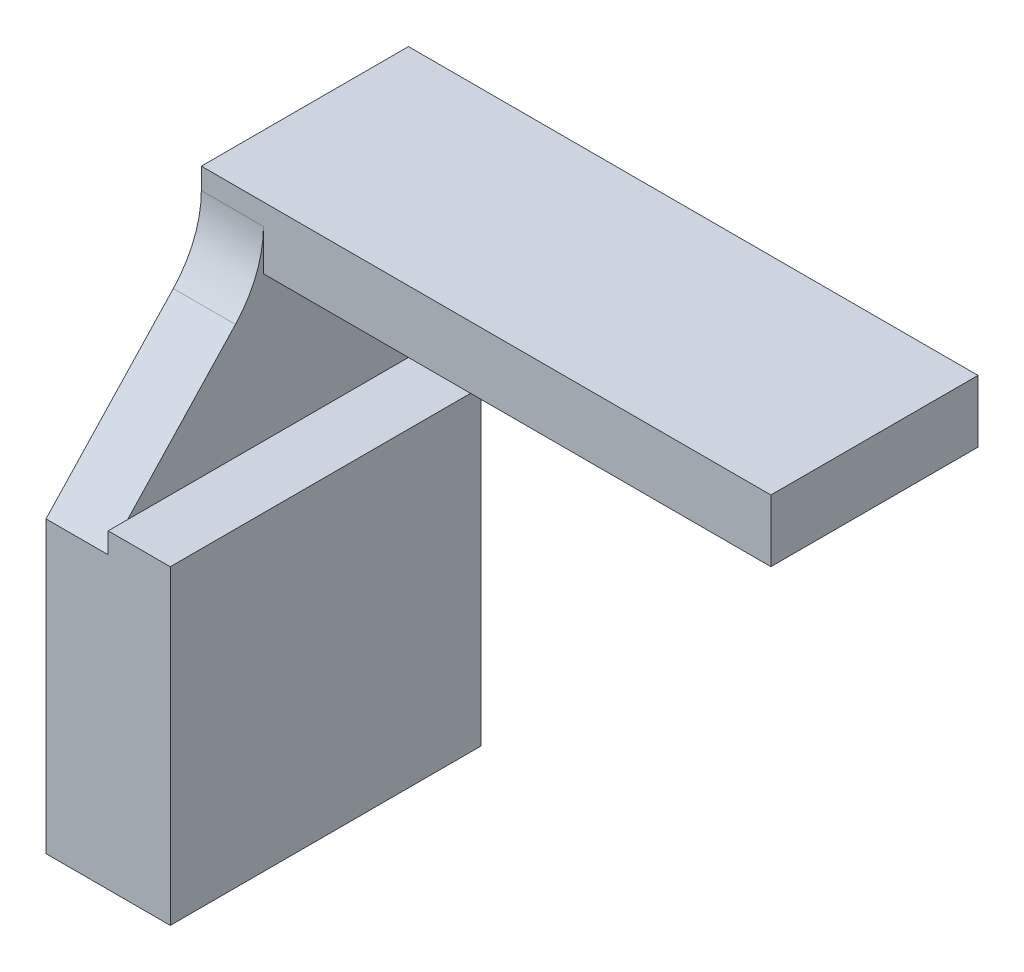
SolidWorks part; units mm, degrees
material "1060 Alloy"
ref_plane "Front Plane" through (0, 0, 0) normal (0, 0, 1) x (1, 0, 0)
ref_plane "Top Plane" through (0, 0, 0) normal (0, 1, 0) x (1, 0, 0)
ref_plane "Right Plane" through (0, 0, 0) normal (1, 0, 0) x (0, 0, -1)
sketch "Sketch1" plane through (0, 0, 0) normal (0, 1, 0) x (1, 0, 0)
  line L1 (-27.5, -10) -> (27.5, -10)
  line L2 (-27.5, -10) -> (-27.5, 10)
  line L3 (-27.5, 10) -> (27.5, 10)
  line L4 (27.5, -10) -> (27.5, 10)
  line L5 (-27.5, -10) -> (27.5, 10) construction
  line L6 (-27.5, 10) -> (27.5, -10) construction
  point P0 (0, 0)
  dimension "D1" = 20
  dimension "D2" = 55
extrude "Boss-Extrude1" add sketch "Sketch1" along normal blind 6
ref_plane "Plane1" through (-27.5, 0, 0) normal (-1, 0, 0) x (0, 0, 1)
sketch "Sketch2" plane through (-27.5, 0, 0) normal (-1, 0, 0) x (0, 0, 1)
  line L0 (10, 0) -> (-10, 0)
  line L1 (-10, 6) -> (-10, 0) construction
  line L2 (-5, -5) -> (-5, -44)
  line L4 (-5, -44) -> (25, -44)
  line L5 (25, -44) -> (25, -16)
  line L6 (25, -16) -> (10, 0)
  line L7 (-10, 0) -> (-5, -5)
  dimension "D1" = 39
  dimension "D2" = 5
  dimension "D3" = 30
  dimension "D4" = 28
  dimension "D5" = 5
extrude "Boss-Extrude2" add sketch "Sketch2" against normal blind 6
fillet "Fillet1" radius 10 1 edges
ref_plane "Plane2" through (-21.5, 0, 0) normal (1, 0, 0) x (0, 0, -1)
sketch "Sketch3" plane through (-21.5, 0, 0) normal (1, 0, 0) x (0, 0, -1)
  line L0 (-25, -44) -> (-25, -16) construction
  line L1 (5, -44) -> (-25, -44)
  line L2 (5, -44) -> (5, -14)
  line L3 (5, -14) -> (-25, -14)
  line L4 (-25, -44) -> (-25, -14)
  dimension "D1" = 30
extrude "Boss-Extrude3" add sketch "Sketch3" along normal blind 6
